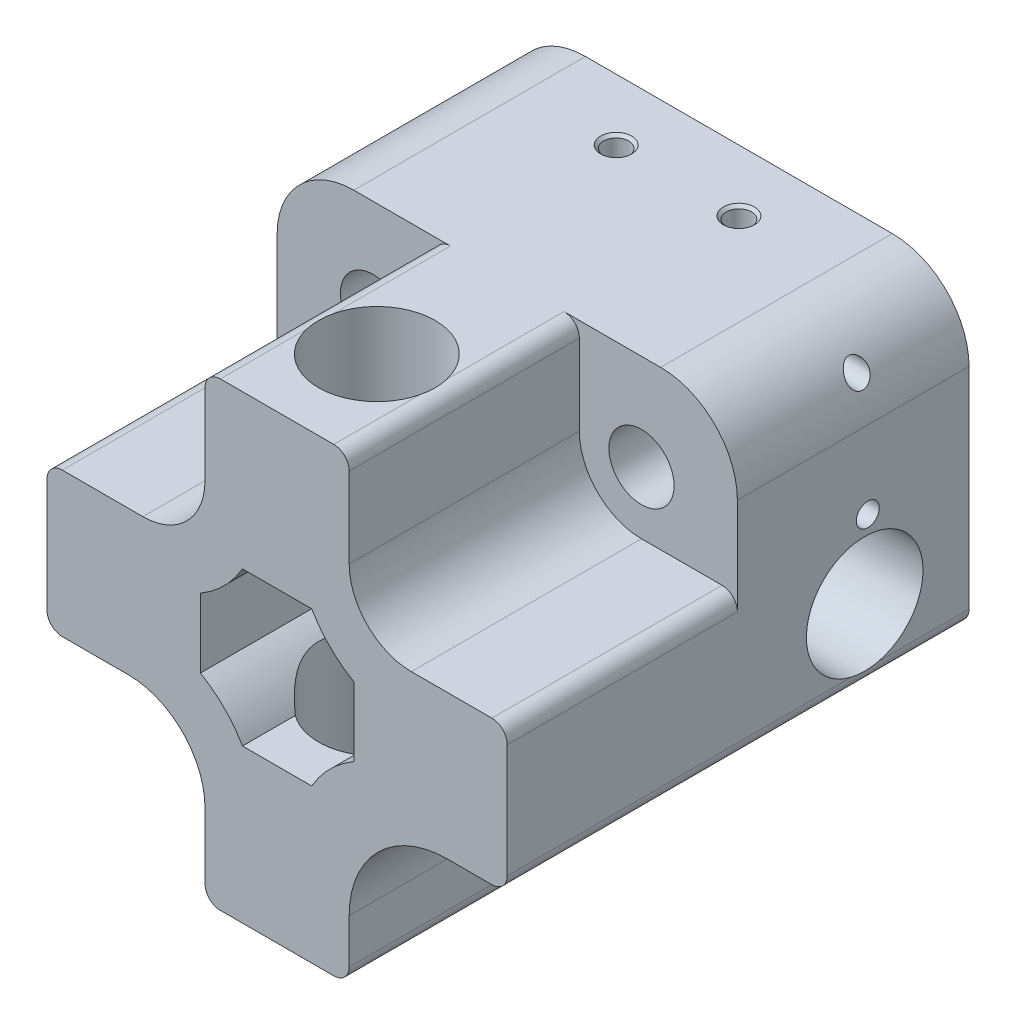
SolidWorks part; units mm, degrees
note: '?' marks a value the reader was unsure of.
material "Lega 1060"
ref_plane "Piano frontale" through (0, 0, 0) normal (0, 0, 1) x (1, 0, 0)
ref_plane "Piano superiore" through (0, 0, 0) normal (0, 1, 0) x (1, 0, 0)
ref_plane "Piano destro" through (0, 0, 0) normal (1, 0, 0) x (0, 0, -1)
sketch "Schizzo1" plane through (0, 0, 0) normal (0, 0, 1) x (1, 0, 0)
  line L0 (-60, 0) -> (-60, 60)
  line L1 (-60, 60) -> (0, 60)
  line L6 (0, 0) -> (0, 60)
  line L7 (0, 0) -> (-60, 0)
  point P0 (0, 0)
  dimension "D1" = 60
extrude "Estrusione-Estrusione1" add sketch "Schizzo1" along normal blind 60.2
sketch "Schizzo2" plane through (0, 0, 0) normal (1, 0, 0) x (0, 0, -1)
  line L2 (-13.6, 30) -> (-47.2, 30) construction
  line L3 (-60.2, 0) -> (0, 0) construction
  line L4 (-60.2, 60) -> (0, 60) construction
  line L5 (-55.2, 30) -> (-60.2, 30) construction
  line L8 (-60.2, 0) -> (-60.2, 60) construction
  circle A0 centre (-13.6, 30) radius 7.6
  circle A1 centre (-47.2, 30) radius 8 construction
  dimension "D1" = 15.2
  dimension "D3" = 16
  dimension "D2" = 33.6
  dimension "D5" = 13
extrude "Taglio-Estrusione1" cut sketch "Schizzo2" against normal through all
sketch "Schizzo3" plane through (0, 60, 0) normal (0, 1, 0) x (0, 0, -1)
  line L0 (-47.2, 30) -> (-20.3794, 30) construction
  line L3 (-60.2, 0) -> (0, 0) construction
  line L7 (-60.2, 60) -> (0, 60) construction
  line L8 (-60.2, 0) -> (-60.2, 60) construction
  circle A0 centre (-47.2, 30) radius 7.6
  dimension "D1" = 15.2
  dimension "D2" = 13
extrude "Taglio-Estrusione2" cut sketch "Schizzo3" against normal through all from surface at 0 starting at face at (-30, 60, 30.1)
sketch "Schizzo4" plane through (0, 0, 60.2) normal (0, 0, 1) x (1, 0, 0)
  line L0 (11.7083, 30) -> (-30, 30) construction
  line L1 (-30, 30) -> (-30, 11.0363) construction
  line L2 (0, 0) -> (0, 60) construction
  line L3 (-60, 60) -> (-60, 0) construction
  line L4 (-60, 0) -> (0, 0) construction
  line L5 (0, 60) -> (-60, 60) construction
  circle A0 centre (-12.5, 12.5) radius 8.1
  circle A1 centre (-47.5, 12.5) radius 8.1
  circle A2 centre (-47.5, 47.5) radius 8.1
  circle A3 centre (-12.5, 47.5) radius 8.1
  point P22 (-30, 30)
  dimension "D1" = 16.2
  dimension "D3" = 12.5
  dimension "D4" = 12.5
  dimension "D2" = 4
extrude "Taglio-Estrusione3" cut sketch "Schizzo4" against normal through all
hole_wizard "Foro Ø2.6 (2.6)-1" [suppressed] positions "Schizzo6" profile "Schizzo5" hole size "Ø2.6" standard "ISO"
sketch "Schizzo6" plane through (0, 60, 0) normal (0, 1, 0) x (1, 0, 0)
  line L0 (0, -60.2) -> (0, 0) construction
  line L1 (0, 0) -> (-60, 0) construction
  line L2 (-60, -60.2) -> (-60, 0) construction
  point P0 (-12.5, -10)
  point P7 (-47.5, -10)
  dimension "D1" = 12.5
  dimension "D2" = 10
  dimension "D3" = 12.5
sketch "Schizzo5" plane through (-12.5, 60, 10) normal (1, 0, 0) x (0, 0, 1)
  line L0 (0, 0) -> (0, 10.7811)
  line L1 (0, 10.7811) -> (1.3, 10)
  line L2 (1.3, 10) -> (1.3, 0)
  line L5 (1.3, 0) -> (0, 0)
  line L10 (0, 10.7811) -> (-1.3, 10) construction
  line L11 (0, -6.35) -> (0, 107.95) construction
  dimension "Hole Dia." = 2.6
  dimension "Hole Depth" = 10
  dimension "Drill Angle" = 118
ref_plane "Piano3" through (0, 30, 0) normal (0, -1, 0) x (-1, 0, 0)
sketch "Schizzo7" plane through (0, 0, 60.2) normal (0, 0, 1) x (1, 0, 0)
  line L0 (-60, 60) -> (-30, 30) construction
  line L1 (-30, 30) -> (-60, 0) construction
  line L2 (-20, 34.5096) -> (-20, 25.4904)
  line L3 (0, 60) -> (-60, 60) construction
  line L4 (-25.4904, 20) -> (-34.5096, 20)
  line L5 (-40, 25.4904) -> (-40, 34.5096)
  line L6 (-34.5096, 40) -> (-25.4904, 40)
  arc A0 (-20, 34.5096) -> (-25.4904, 40) centre (-12.5, 47.5) cw
  arc A1 (-20, 25.4904) -> (-25.4904, 20) centre (-12.5, 12.5) ccw
  arc A2 (-34.5096, 20) -> (-40, 25.4904) centre (-47.5, 12.5) ccw
  arc A3 (-34.5096, 40) -> (-40, 34.5096) centre (-47.5, 47.5) cw
  circle A4 centre (-12.5, 47.5) radius 8.1 construction
  circle A5 centre (-12.5, 47.5) radius 8.1 construction
  circle A6 centre (-47.5, 47.5) radius 8.1 construction
  circle A7 centre (-47.5, 47.5) radius 8.1 construction
  circle A8 centre (-47.5, 12.5) radius 8.1 construction
  circle A9 centre (-47.5, 12.5) radius 8.1 construction
  circle A13 centre (-12.5, 12.5) radius 8.1 construction
  circle A14 centre (-12.5, 12.5) radius 8.1 construction
  dimension "D1" = 20
  dimension "D2" = 15
extrude "Taglio-Estrusione4" cut sketch "Schizzo7" against normal through all
fillet "Raccordo1" radius 10 4 edges at (-60, 60, 30.1) (-60, 0, 30.1) (0, 60, 30.1) (0, 0, 30.1)
sketch "Schizzo8" plane through (0, 0, 60.2) normal (0, 0, 1) x (1, 0, 0)
  line L0 (-47.5, 20.6) -> (-58, 20.6)
  line L1 (-60, 50) -> (-60, 10) construction
  line L2 (-39.4, 12.5) -> (-39.4, 2)
  line L3 (-34.3179, 30) -> (-30, 30) construction
  line L4 (-60, 22.6) -> (-60, 10)
  line L5 (-50, 0) -> (-37.4, 0)
  line L6 (-30, 30) -> (-30, 35.3582) construction
  line L7 (0, 10) -> (0, 50) construction
  line L8 (-50, 0) -> (-10, 0) construction
  line L9 (-10, 60) -> (-50, 60) construction
  line L10 (-39.4, 47.5) -> (-39.4, 58)
  line L11 (-47.5, 39.4) -> (-58, 39.4)
  line L12 (-37.4, 60) -> (-50, 60)
  line L13 (-60, 50) -> (-60, 37.4)
  line L14 (-30, 30) -> (-24.6418, 30) construction
  line L15 (-12.5, 39.4) -> (-2, 39.4)
  line L16 (-20.6, 47.5) -> (-20.6, 58)
  line L17 (0, 37.4) -> (0, 50)
  line L18 (-10, 60) -> (-22.6, 60)
  line L19 (-30, 30) -> (-30, 24.6418) construction
  line L20 (-20.6, 12.5) -> (-20.6, 2)
  line L21 (-12.5, 20.6) -> (-2, 20.6)
  line L22 (-22.6, 0) -> (-10, 0)
  line L23 (0, 10) -> (0, 22.6)
  line L24 (-30, 30) -> (-35.3582, 30) construction
  line L25 (-39.4, 47.5) -> (-39.4, 58) [skipped]
  line L26 (-37.4, 60) -> (-50, 60) [skipped]
  line L27 (-60, 50) -> (-60, 37.4) [skipped]
  line L28 (-47.5, 39.4) -> (-58, 39.4) [skipped]
  line L29 (-12.5, 39.4) -> (-2, 39.4) [skipped]
  line L30 (0, 37.4) -> (0, 50) [skipped]
  line L31 (-10, 60) -> (-22.6, 60) [skipped]
  line L32 (-20.6, 47.5) -> (-20.6, 58) [skipped]
  line L33 (-20.6, 12.5) -> (-20.6, 2) [skipped]
  line L34 (-22.6, 0) -> (-10, 0) [skipped]
  line L35 (0, 10) -> (0, 22.6) [skipped]
  line L36 (-12.5, 20.6) -> (-2, 20.6) [skipped]
  arc A0 (-47.5, 20.6) -> (-39.4, 12.5) centre (-47.5, 12.5) cw
  circle A1 centre (-47.5, 12.5) radius 8.1 construction
  arc A2 (-39.4, 2) -> (-37.4, 0) centre (-37.4, 2) ccw
  arc A3 (-58, 20.6) -> (-60, 22.6) centre (-58, 22.6) cw
  arc A4 (-60, 10) -> (-50, 0) centre (-50, 10) ccw
  arc A5 (-60, 10) -> (-50, 0) centre (-50, 10) ccw construction
  arc A6 (-39.4, 47.5) -> (-47.5, 39.4) centre (-47.5, 47.5) cw
  arc A7 (-58, 39.4) -> (-60, 37.4) centre (-58, 37.4) ccw
  arc A8 (-39.4, 58) -> (-37.4, 60) centre (-37.4, 58) cw
  arc A9 (-50, 60) -> (-60, 50) centre (-50, 50) ccw
  arc A10 (-12.5, 39.4) -> (-20.6, 47.5) centre (-12.5, 47.5) cw
  arc A11 (-20.6, 58) -> (-22.6, 60) centre (-22.6, 58) ccw
  arc A12 (-2, 39.4) -> (0, 37.4) centre (-2, 37.4) cw
  arc A13 (0, 50) -> (-10, 60) centre (-10, 50) ccw
  arc A14 (-20.6, 12.5) -> (-12.5, 20.6) centre (-12.5, 12.5) cw
  arc A15 (-2, 20.6) -> (0, 22.6) centre (-2, 22.6) ccw
  arc A16 (-20.6, 2) -> (-22.6, 0) centre (-22.6, 2) cw
  arc A17 (-10, 0) -> (0, 10) centre (-10, 10) ccw
  arc A18 (-39.4, 58) -> (-37.4, 60) centre (-37.4, 58) cw [skipped]
  arc A19 (-50, 60) -> (-60, 50) centre (-50, 50) ccw [skipped]
  arc A20 (-58, 39.4) -> (-60, 37.4) centre (-58, 37.4) ccw [skipped]
  arc A21 (-2, 39.4) -> (0, 37.4) centre (-2, 37.4) cw [skipped]
  arc A22 (0, 50) -> (-10, 60) centre (-10, 50) ccw [skipped]
  arc A23 (-20.6, 58) -> (-22.6, 60) centre (-22.6, 58) ccw [skipped]
  arc A24 (-20.6, 2) -> (-22.6, 0) centre (-22.6, 2) cw [skipped]
  arc A25 (-10, 0) -> (0, 10) centre (-10, 10) ccw [skipped]
  arc A26 (-2, 20.6) -> (0, 22.6) centre (-2, 22.6) ccw [skipped]
  point P67 (-30, 30)
  point P122 (-30, 30)
  dimension "D1" = 2
  dimension "D2" = 4
  dimension "D3" = 4
extrude "Taglio-Estrusione5" cut sketch "Schizzo8" against normal blind 30
sketch "Schizzo10" plane through (0, 0, 30.2) normal (0, 0, 1) x (1, 0, 0)
  circle A0 centre (-47.5, 47.5) radius 8.1
  circle A5 centre (-12.5, 47.5) radius 8.1
  arc A6 (-12.5, 39.4) -> (-20.6, 47.5) centre (-12.5, 47.5) ccw construction
  arc A7 (-39.4, 47.5) -> (-47.5, 39.4) centre (-47.5, 47.5) ccw construction
extrude "Estrusione-Estrusione3" add sketch "Schizzo10" against normal blind 10
sketch "Schizzo13" plane through (0, 0, 30.2) normal (0, 0, 1) x (1, 0, 0)
  circle A0 centre (-12.5, 47.5) radius 4.25
  circle A1 centre (-47.5, 47.5) radius 4.25
  circle A4 centre (-12.5, 47.5) radius 8.1 construction
  circle A5 centre (-47.5, 47.5) radius 8.1 construction
  dimension "D1" = 8.5
extrude "Taglio-Estrusione6" cut sketch "Schizzo13" against normal blind 9.8
ref_plane "Piano4" through (-30, 0, 0) normal (-1, 0, 0) x (0, 0, 1)
ref_plane "Piano5" through (0, 30, 0) normal (0, -1, 0) x (-1, 0, 0)
ref_axis "Assi1" through (-30, 30, 16.664) along (0, 0, 1)?
pattern_circular "RipetizioneCircolare1" [suppressed] count 4 over 360 about axis through (-30, 30, 16.664) along (0, 0, 1)
sketch "Schizzo14" plane through (0, 0, 30.2) normal (0, 0, 1) x (1, 0, 0)
  line L0 (-20.6, 12.5) -> (-20.6, 2) construction
  line L1 (-22.6, 0) -> (-10, 0) construction
  line L2 (0, 10) -> (0, 22.6) construction
  line L3 (-2, 20.6) -> (-12.5, 20.6) construction
  line L4 (-47.5, 20.6) -> (-58, 20.6)
  line L5 (-60, 22.6) -> (-60, 10)
  line L6 (-50, 0) -> (-37.4, 0)
  line L7 (-39.4, 2) -> (-39.4, 12.5)
  line L8 (-47.5, 20.6) -> (-58, 20.6)
  line L9 (-60, 22.6) -> (-60, 10)
  line L10 (-50, 0) -> (-37.4, 0)
  line L11 (-39.4, 2) -> (-39.4, 12.5)
  line L12 (-20.6, 12.5) -> (-20.6, 2)
  line L13 (-22.6, 0) -> (-10, 0)
  line L14 (0, 10) -> (0, 22.6)
  line L15 (-2, 20.6) -> (-12.5, 20.6)
  arc A0 (-39.4, 12.5) -> (-47.5, 20.6) centre (-47.5, 12.5) ccw construction
  arc A2 (-39.4, 12.5) -> (-47.5, 20.6) centre (-47.5, 12.5) ccw
  arc A4 (-47.5, 20.6) -> (-39.4, 12.5) centre (-47.5, 12.5) ccw
  arc A5 (-60, 22.6) -> (-58, 20.6) centre (-58, 22.6) ccw
  arc A6 (-60, 10) -> (-50, 0) centre (-50, 10) ccw
  arc A7 (-39.4, 2) -> (-37.4, 0) centre (-37.4, 2) ccw
  arc A8 (-47.5, 20.6) -> (-39.4, 12.5) centre (-47.5, 12.5) ccw
  arc A9 (-60, 22.6) -> (-58, 20.6) centre (-58, 22.6) ccw
  arc A10 (-60, 10) -> (-50, 0) centre (-50, 10) ccw
  arc A11 (-39.4, 2) -> (-37.4, 0) centre (-37.4, 2) ccw
  arc A12 (-39.4, 12.5) -> (-47.5, 20.6) centre (-47.5, 12.5) ccw
  arc A13 (-10, 0) -> (0, 10) centre (-10, 10) ccw construction
  arc A14 (-22.6, 0) -> (-20.6, 2) centre (-22.6, 2) ccw construction
  arc A15 (-2, 20.6) -> (0, 22.6) centre (-2, 22.6) ccw construction
  arc A17 (-10, 0) -> (0, 10) centre (-10, 10) ccw
  arc A18 (-22.6, 0) -> (-20.6, 2) centre (-22.6, 2) ccw
  arc A19 (-2, 20.6) -> (0, 22.6) centre (-2, 22.6) ccw
  arc A20 (-12.5, 20.6) -> (-20.6, 12.5) centre (-12.5, 12.5) ccw construction
  arc A21 (-12.5, 20.6) -> (-20.6, 12.5) centre (-12.5, 12.5) ccw
  dimension "D1" = 0
extrude "Taglio-Estrusione7" cut sketch "Schizzo14" against normal up to next (30.2 mm away) and the other way up to next (30 mm away) contours L15 A21 L12 A18 L13 A17 L14 A19
sketch "Schizzo15" plane through (0, 0, 60.2) normal (0, 0, 1) x (1, 0, 0)
  line L0 (-25.4982, 25.4982) -> (0, 0) construction
  line L1 (-37.4, 0) -> (-22.6, 0) construction
  line L2 (0, 22.6) -> (0, 37.4) construction
  line L5 (-20.6, 12.5) -> (-20.6, 7.8)
  line L6 (-7.8, 20.6) -> (-12.5, 20.6)
  line L7 (-47.5, 20.6) -> (-58, 20.6) construction
  line L8 (-2, 20.6) -> (-12.5, 20.6) construction
  line L9 (-39.4, 2) -> (-39.4, 12.5) construction
  line L10 (-20.6, 12.5) -> (-20.6, 2) construction
  line L11 (-47.5, 20.6) -> (-58, 20.6) construction
  line L12 (-49.4, 20.6) -> (-47.5, 20.6)
  line L13 (-39.4, 12.5) -> (-39.4, 10.6)
  arc A0 (-7.8, 20.6) -> (-20.6, 7.8) centre (-7.8, 7.8) ccw
  arc A1 (-12.5, 20.6) -> (-20.6, 12.5) centre (-12.5, 12.5) ccw construction
  arc A2 (-12.5, 20.6) -> (-20.6, 12.5) centre (-12.5, 12.5) ccw
  arc A3 (-49.4, 20.6) -> (-39.4, 10.6) centre (-49.4, 10.6) cw
  arc A4 (-39.4, 12.5) -> (-47.5, 20.6) centre (-47.5, 12.5) ccw
  arc A6 (-39.4, 12.5) -> (-47.5, 20.6) centre (-47.5, 12.5) ccw construction
  dimension "D1" = 25.6
  dimension "D2" = 10
extrude "Estrusione-Estrusione4" add sketch "Schizzo15" against normal through all
hole_wizard "Foro Ø2.6 (2.6)-2" positions "Schizzo19" profile "Schizzo18" hole size "Ø2.6" standard "ISO"
sketch "Schizzo19" plane through (0, 0, 0) normal (0, 0, -1) x (-1, 0, 0)
  line L0 (30, 35.2948) -> (30, -6.7357) construction
  line L4 (30, 30) -> (0, 0) construction
  line L7 (2, 20.6) -> (7.8, 20.6) construction
  line L8 (20.6, 7.8) -> (20.6, 2) construction
  line L9 (39.4, 2) -> (39.4, 10.6) construction
  point P0 (24.1, 16.1)
  point P2 (16.1, 24.1)
  point P4 (35.9, 16.1)
  point P6 (43.9, 24.1)
  dimension "D1" = 8
  dimension "D2" = 3.5
sketch "Schizzo18" plane through (-24.1, 16.1, 0) normal (1, 0, 0) x (0, 1, 0)
  line L0 (0, 0) -> (0, 10.7811)
  line L1 (0, 10.7811) -> (1.3, 10)
  line L2 (1.3, 10) -> (1.3, 0)
  line L5 (1.3, 0) -> (0, 0)
  line L10 (0, 10.7811) -> (-1.3, 10) construction
  line L11 (0, -6.35) -> (0, 107.95) construction
  dimension "Hole Dia." = 2.6
  dimension "Hole Depth" = 10
  dimension "Drill Angle" = 118
sketch "Schizzo20" plane through (0, 0, 0) normal (1, 0, 0) x (0, 0, -1)
  line L0 (-20.2, 39.4) -> (-20.2, 55.6) construction
  line L1 (-20.2, 39.4) -> (0, 39.4) construction
  circle A0 centre (-13.2, 39.9) radius 1.5
  dimension "D3" = 3
  dimension "D1" = 7
  dimension "D2" = 0.5
extrude "Taglio-Estrusione8" cut sketch "Schizzo20" against normal blind 71
sketch "Schizzo22" plane through (0, 0, 0) normal (1, 0, 0) x (0, 0, -1)
  line L0 (-20.2, 39.4) -> (-20.2, 55.6) construction
  line L1 (0, 55.6) -> (-20.2, 55.6) construction
  circle A1 centre (-13.2, 55.1) radius 1.5
  dimension "D3" = 3
  dimension "D1" = 7
  dimension "D2" = 0.5
extrude "Taglio-Estrusione9" cut sketch "Schizzo22" against normal blind 71
sketch "Schizzo24" plane through (0, 60, 0) normal (0, 1, 0) x (1, 0, 0)
  line L0 (-30, -16.664) -> (-30, -62.2731) construction
  line L1 (-10, 0) -> (-50, 0) construction
  point P0 (-38, -8)
  point P1 (-22, -8)
  dimension "D1" = 8
  dimension "D2" = 8
  dimension "D3" = 8
  dimension "D4" = 8
hole_wizard "Foro filettato M4x0.7-1" positions "Schizzo26" profile "Schizzo25" tap size "M4x0.7" standard "Ansi Metric"
sketch "Schizzo26" plane through (0, 60, 0) normal (0, 1, 0) x (1, 0, 0)
  point P0 (-38, -8)
  point P3 (-22, -8)
sketch "Schizzo25" plane through (-38, 60, 8) normal (1, 0, 0) x (0, 0, 1)
  line L0 (0, 0) -> (0, 12.4914)
  line L1 (0, 12.4914) -> (1.65, 11.5)
  line L2 (1.65, 11.5) -> (1.65, 0.375)
  line L3 (1.65, 0.375) -> (2.025, 0)
  line L5 (2.025, 0) -> (0, 0)
  line L6 (-1.65, 0.375) -> (-2.025, 0) construction
  line L10 (0, 12.4914) -> (-1.65, 11.5) construction
  line L11 (0, -6.35) -> (0, 107.95) construction
  dimension "Tap Drill Dia." = 3.3
  dimension "Tap Drill Depth" = 11.5
  dimension "Near C'Sink Dia." = 4.05
  dimension "Near C'Sink Angle" = 90
  dimension "Drill Angle" = 118
cosmetic thread "Filettatura del foro1" parameters "D1"=8, "D2"=4
cosmetic thread "Filettatura del foro2" parameters "D1"=8, "D2"=4
